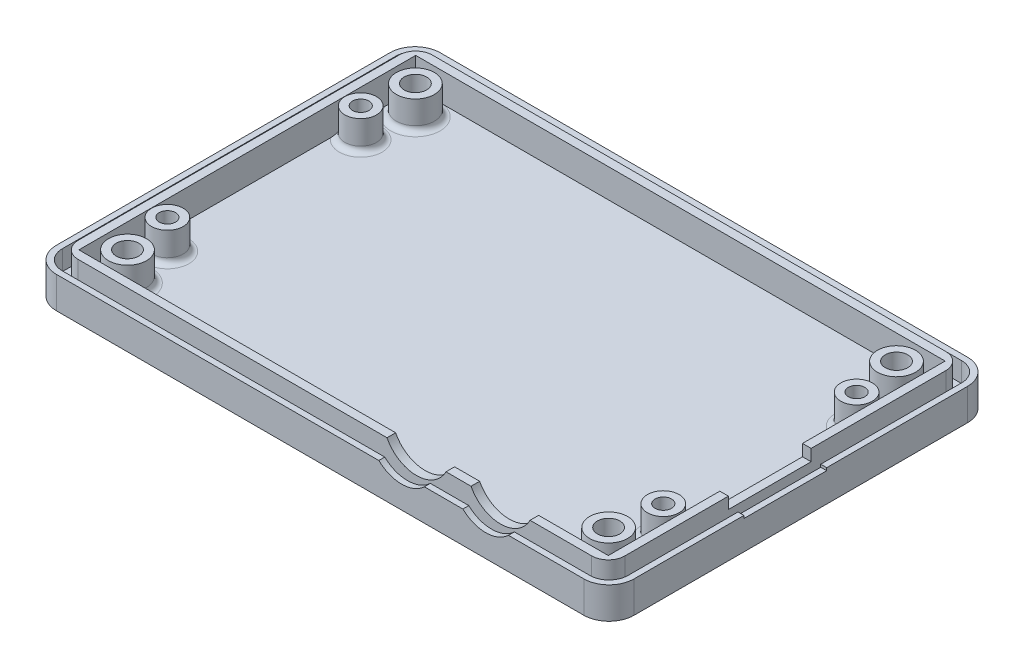
SolidWorks part; units mm, degrees
ref_plane "Front Plane" through (0, 0, 0) normal (0, 0, 1) x (1, 0, 0)
ref_plane "Top Plane" through (0, 0, 0) normal (0, 1, 0) x (1, 0, 0)
ref_plane "Right Plane" through (0, 0, 0) normal (1, 0, 0) x (0, 0, -1)
sketch "Sketch1" plane through (0, 0, 0) normal (0, 1, 0) x (1, 0, 0)
  line L1 (-38.7187, 32.9806) -> (48.5813, 32.9806)
  line L2 (-38.7187, 32.9806) -> (-38.7187, -25.0194)
  line L3 (-38.7187, -25.0194) -> (48.5813, -25.0194)
  line L4 (48.5813, 32.9806) -> (48.5813, -25.0194)
  dimension "D1" = 58
  dimension "D2" = 87.3
extrude "Boss-Extrude1" add sketch "Sketch1" along normal blind 1.77
fillet "Fillet1" radius 3.8 4 edges at (48.5813, 0.885, 25.0194) (48.5813, 0.885, -32.9806) (-38.7187, 0.885, -32.9806) (-38.7187, 0.885, 25.0194)
sketch "Sketch2" plane through (0, 1.77, 0) normal (0, 1, 0) x (1, 0, 0)
  line L22 (44.7813, 32.9806) -> (-34.9187, 32.9806)
  line L23 (-38.7187, 29.1806) -> (-38.7187, -21.2194)
  line L24 (-34.9187, -25.0194) -> (44.7813, -25.0194)
  line L25 (48.5813, -21.2194) -> (48.5813, 29.1806)
  line L26 (47.6813, -21.2194) -> (47.6813, 29.1806)
  line L27 (44.7813, 32.0806) -> (-34.9187, 32.0806)
  line L28 (-34.9187, -24.1194) -> (44.7813, -24.1194)
  line L29 (-37.8187, 29.1806) -> (-37.8187, -21.2194)
  line L30 (47.6813, -21.2194) -> (47.6813, 29.1806)
  line L31 (44.7813, 32.0806) -> (-34.9187, 32.0806)
  line L32 (-34.9187, -24.1194) -> (44.7813, -24.1194)
  line L33 (-37.8187, 29.1806) -> (-37.8187, -21.2194)
  arc A14 (-34.9187, 32.9806) -> (-38.7187, 29.1806) centre (-34.9187, 29.1806) ccw
  arc A15 (-38.7187, -21.2194) -> (-34.9187, -25.0194) centre (-34.9187, -21.2194) ccw
  arc A16 (44.7813, -25.0194) -> (48.5813, -21.2194) centre (44.7813, -21.2194) ccw
  arc A17 (48.5813, 29.1806) -> (44.7813, 32.9806) centre (44.7813, 29.1806) ccw
  arc A18 (44.7813, -24.1194) -> (47.6813, -21.2194) centre (44.7813, -21.2194) ccw
  arc A19 (47.6813, 29.1806) -> (44.7813, 32.0806) centre (44.7813, 29.1806) ccw
  arc A20 (-34.9187, 32.0806) -> (-37.8187, 29.1806) centre (-34.9187, 29.1806) ccw
  arc A21 (-37.8187, -21.2194) -> (-34.9187, -24.1194) centre (-34.9187, -21.2194) ccw
  arc A22 (44.7813, -24.1194) -> (47.6813, -21.2194) centre (44.7813, -21.2194) ccw
  arc A23 (47.6813, 29.1806) -> (44.7813, 32.0806) centre (44.7813, 29.1806) ccw
  arc A24 (-34.9187, 32.0806) -> (-37.8187, 29.1806) centre (-34.9187, 29.1806) ccw
  arc A25 (-37.8187, -21.2194) -> (-34.9187, -24.1194) centre (-34.9187, -21.2194) ccw
  dimension "D3" = 87.3
  dimension "D1" = 0.9
  dimension "D2" = 0.9
extrude "Boss-Extrude2" add sketch "Sketch2" along normal blind 3
sketch "Sketch3" plane through (0, 1.77, 0) normal (0, 1, 0) x (1, 0, 0)
  line L0 (44.9313, -9.8465) -> (47.6813, -9.8465) construction
  line L1 (-35.0687, 29.4306) -> (44.9313, 29.4306)
  line L2 (-35.0687, 29.4306) -> (-35.0687, -21.4694)
  line L3 (-35.0687, -21.4694) -> (44.9313, -21.4694)
  line L4 (44.9313, 29.4306) -> (44.9313, -21.4694)
  line L5 (47.6813, -21.2194) -> (47.6813, 29.1806) construction
  line L6 (-35.0687, -9.8465) -> (-37.8187, -9.8465)
  line L7 (-37.8187, 29.1806) -> (-37.8187, -21.2194) construction
  line L9 (-30.0419, 29.4306) -> (-30.0419, 32.0806) construction
  line L10 (44.7813, 32.0806) -> (-34.9187, 32.0806) construction
  line L11 (-26.9492, -21.4694) -> (-26.9492, -24.1194) construction
  line L12 (-34.9187, -24.1194) -> (44.7813, -24.1194) construction
  line L13 (-36.3687, 30.7306) -> (46.2313, 30.7306)
  line L14 (46.2313, 30.7306) -> (46.2313, -22.7694)
  line L15 (-36.3687, -22.7694) -> (46.2313, -22.7694)
  line L16 (-36.3687, 30.7306) -> (-36.3687, -22.7694)
  dimension "D1" = 50.9
  dimension "D2" = 80
  dimension "D3" = 1.3
  dimension "D4" = 53.5
  dimension "D5" = 82.6
extrude "Boss-Extrude3" add sketch "Sketch3" along normal blind 4.35 contours L13 L16 L2 L1 L4 L3 L15 L14 region at (-35.3846, 1.77, -10.4421)
fillet "Fillet2" radius 2.5 4 edges at (-36.3687, 3.945, 22.7694) (46.2313, 3.945, 22.7694) (46.2313, 3.945, -30.7306) (-36.3687, 3.945, -30.7306)
sketch "Sketch4" plane through (0, 1.77, 0) normal (0, 1, 0) x (1, 0, 0)
  line L1 (-31.4187, -17.7694) -> (-31.4187, -21.4694) construction
  line L2 (-35.0687, -21.4694) -> (44.9313, -21.4694) construction
  line L3 (-31.4187, 25.7306) -> (-31.4187, 29.4306)
  line L4 (-35.0687, 29.4306) -> (44.9313, 29.4306) construction
  line L6 (-31.4187, 25.7306) -> (-35.0687, 25.7306) construction
  line L7 (-35.0687, 29.4306) -> (-35.0687, -21.4694) construction
  line L8 (41.2813, 25.7306) -> (44.9313, 25.7306) construction
  line L9 (44.9313, 29.4306) -> (44.9313, -21.4694) construction
  circle A0 centre (-31.4187, -17.7694) radius 2.875
  circle A1 centre (41.2813, -17.7694) radius 2.875
  circle A2 centre (41.2813, 25.7306) radius 2.875
  circle A3 centre (-31.4187, 25.7306) radius 2.875
  dimension "D1" = 5.75
  dimension "D4" = 72.7
  dimension "D5" = 43.5
  dimension "D2" = 2
  dimension "D3" = 2
extrude "Boss-Extrude4" add sketch "Sketch4" along normal blind 4.35 contours A0 | A1 | A2 | A3 region at (-31.4187, 1.77, 17.7694) region at (41.2813, 1.77, 17.7694) region at (41.2813, 1.77, -25.7306)
sketch "Sketch5" plane through (0, 6.12, 0) normal (0, 1, 0) x (1, 0, 0)
  circle A0 centre (-31.4187, 25.7306) radius 1.7
  circle A1 centre (41.2813, 25.7306) radius 1.7
  circle A2 centre (-31.4187, -17.7694) radius 1.7
  circle A3 centre (41.2813, -17.7694) radius 1.7
  dimension "D1" = 3.4
  dimension "D2" = 3.4
  dimension "D3" = 3.4
  dimension "D4" = 3.4
extrude "Cut-Extrude1" cut sketch "Sketch5" against normal blind 6.22
chamfer "Chamfer1" distance 1.45 angle 45 4 edges at (41.2813, 0, -24.0306) (-31.4187, 0, -24.0306) (41.2813, 0, 19.4694) (-31.4187, 0, 19.4694)
sketch "Sketch6" plane through (0, 1.77, 0) normal (0, 1, 0) x (1, 0, 0)
  line L2 (-32.5337, 18.5856) -> (-35.0687, 18.5856)
  line L3 (-35.0687, 29.4306) -> (-35.0687, -21.4694) construction
  line L4 (42.3963, 18.5856) -> (44.9313, 18.5856)
  line L5 (44.9313, 29.4306) -> (44.9313, -21.4694) construction
  line L6 (-32.5337, 18.5856) -> (-32.5337, 29.4306) construction
  line L7 (-35.0687, 29.4306) -> (44.9313, 29.4306) construction
  line L8 (-32.5337, -10.6244) -> (-32.5337, -21.4694)
  line L9 (-35.0687, -21.4694) -> (44.9313, -21.4694) construction
  circle A0 centre (-32.5337, -10.6244) radius 2.39
  circle A1 centre (42.3963, -10.6244) radius 2.39
  circle A2 centre (42.3963, 18.5856) radius 2.39
  circle A3 centre (-32.5337, 18.5856) radius 2.39
  circle A4 centre (-32.5337, 18.5856) radius 1.24
  circle A5 centre (42.3963, 18.5856) radius 1.24
  circle A6 centre (-32.5337, -10.6244) radius 1.24
  circle A7 centre (42.3963, -10.6244) radius 1.24
  dimension "D1" = 4.78
  dimension "D6" = 2.48
  dimension "D4" = 74.93
  dimension "D5" = 29.21
  dimension "D2" = 2
  dimension "D3" = 2
extrude "Boss-Extrude5" add sketch "Sketch6" along normal blind 4.45 contours L6 A4 L2 A3 | A4 L6 A3 L2 | A6 A0 | A5 A2 | A1 A7 region at (-32.5337, 1.77, -17.278) region at (-33.7279, 1.77, -19.7797) region at (40.0739, 1.77, -18.5856) region at (-34.1759, 1.77, 8.9822) region at (40.0739, 1.77, 10.6244)
fillet "Fillet3" radius 0.85 8 edges at (-31.4187, 1.77, 20.6444) (-32.5337, 1.77, 13.0144) (41.2813, 1.77, 20.6444) (42.3963, 1.77, 13.0144) (-32.5337, 1.77, -16.1956) (-31.4187, 1.77, -22.8556) (42.3963, 1.77, -16.1956) (41.2813, 1.77, -22.8556)
sketch "Sketch7" plane through (0, 0, 25.0194) normal (0, 0, 1) x (1, 0, 0)
  line L0 (-34.9187, 4.77) -> (44.7813, 4.77)
  line L1 (4.9313, 4.77) -> (4.9313, 17.4274)
  line L2 (29.9503, 4.77) -> (29.9503, 17.4274)
  line L3 (29.9503, 7.7075) -> (32.98, 7.7075)
  line L4 (29.9503, 8.4075) -> (32.1066, 8.4075)
  line L5 (-35.0687, 6.12) -> (44.9313, 6.12) construction
  line L6 (17.2503, 4.77) -> (17.2503, 19.4054)
  line L7 (29.9503, 8.4075) -> (17.2503, 8.4075)
  circle A0 centre (29.9503, 8.4075) radius 4.01
  circle A1 centre (29.9503, 8.4075) radius 5.01
  circle A2 centre (17.2503, 8.4075) radius 5.01
  dimension "D4" = 8.02
  dimension "D9" = 10.02
  dimension "D2" = 1.5875
  dimension "D3" = 0.7
  dimension "D6" = 12.319
  dimension "D7" = 3.6375
  dimension "D8" = 25.019
  dimension "D1" = 25.019
  dimension "D5" = 1
extrude "Cut-Extrude2" cut sketch "Sketch7" against normal blind 4.45 contours A1 | A2
sketch "Sketch8" plane through (48.5813, 0, 0) normal (1, 0, 0) x (0, 0, -1)
  line L0 (3.9806, 0) -> (3.9806, 13.0226)
  line L1 (-21.2194, 0) -> (29.1806, 0) construction
  line L2 (2.9806, 0) -> (2.9806, 13.0226)
  line L3 (3.9806, 6.12) -> (2.9806, 6.12)
  line L4 (28.2306, 6.12) -> (-20.2694, 6.12) construction
  line L5 (2.9806, 6.12) -> (-4.6194, 6.12)
  line L6 (-4.6194, 6.12) -> (-4.6194, 4.37)
  line L7 (-4.6194, 4.37) -> (7.8806, 4.37)
  line L8 (7.8806, 4.37) -> (7.8806, 6.12)
  line L9 (7.8806, 6.12) -> (2.9806, 6.12)
  line M2 (29.1806, 4.77) -> (-21.2194, 4.77)
  dimension "D2" = 7.6
  dimension "D3" = 12.5
  dimension "D4" = 1.75
  dimension "D5" = 8.6
  dimension "D1" = 1
extrude "Cut-Extrude3" cut sketch "Sketch8" against normal up to surface (3.65 mm away) contours L5 L6 L2 M2 | L6 L7 L2 M2 | L2 L7 L0 M2 | L0 L3 L2 M2 | L8 L9 L0 M2 | L7 L8 L0 M2 region at (48.5813, 4.57, -3.4806) region at (48.5813, 4.57, -5.9306) region at (48.5813, 5.445, -3.4806) region at (48.5813, 5.445, -5.9306) region at (48.5813, 4.57, 0.8194) region at (48.5813, 5.445, 0.8194) up to face at (44.9313, 2.5579, -3.9719)
